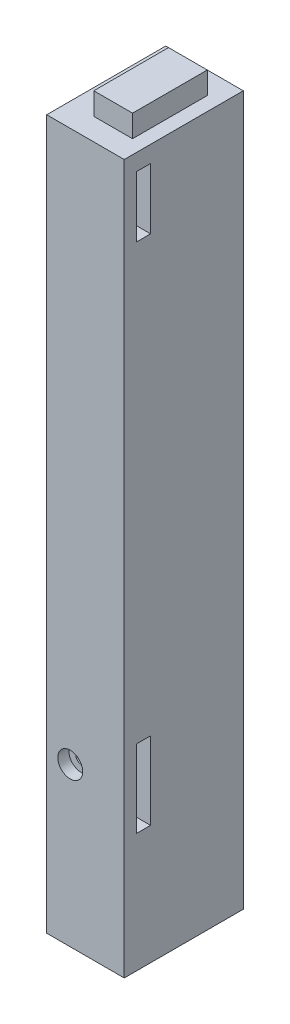
SolidWorks part; units mm, degrees
ref_plane "Front Plane" through (0, 0, 0) normal (0, 0, 1) x (1, 0, 0)
ref_plane "Top Plane" through (0, 0, 0) normal (0, 1, 0) x (1, 0, 0)
ref_plane "Right Plane" through (0, 0, 0) normal (1, 0, 0) x (0, 0, -1)
sketch "Sketch1" plane through (0, 0, 0) normal (0, 0, 1) x (1, 0, 0)
  line L1 (44.45, 406.4) -> (-44.45, 406.4)
  line L2 (44.45, 406.4) -> (44.45, -406.4)
  line L3 (44.45, -406.4) -> (-44.45, -406.4)
  line L4 (-44.45, 406.4) -> (-44.45, -406.4)
  line L5 (44.45, 406.4) -> (-44.45, -406.4) construction
  line L6 (44.45, -406.4) -> (-44.45, 406.4) construction
  point P0 (0, 0)
  dimension "D1" = 812.8
  dimension "D2" = 88.9
extrude "Boss-Extrude1" add sketch "Sketch1" along normal blind 136.525
sketch "Sketch2" plane through (0, 406.4, 0) normal (0, 1, 0) x (1, 0, 0)
  line L0 (-44.45, -136.525) -> (-44.45, 0) construction
  line L1 (-15.875, -25.4) -> (28.575, -25.4)
  line L2 (-15.875, -25.4) -> (-15.875, -111.125)
  line L3 (-15.875, -111.125) -> (28.575, -111.125)
  line L4 (28.575, -25.4) -> (28.575, -111.125)
  line L5 (-15.875, -25.4) -> (28.575, -111.125) construction
  line L6 (-15.875, -111.125) -> (28.575, -25.4) construction
  line L7 (44.45, 0) -> (-44.45, 0) construction
  point P0 (6.35, -68.2625)
  dimension "D1" = 85.725
  dimension "D2" = 28.575
  dimension "D3" = 44.45
  dimension "D4" = 25.4
extrude "Boss-Extrude2" add sketch "Sketch2" along normal blind 25.4 contours L2 L3 L4 L1
sketch "Sketch4" plane through (44.45, 0, 0) normal (1, 0, 0) x (0, 0, -1)
  line L0 (-136.525, 406.4) -> (0, 406.4) construction
  line L1 (-122.2375, -180.975) -> (-106.3625, -180.975)
  line L2 (-122.2375, -180.975) -> (-122.2375, -269.875)
  line L3 (-122.2375, -269.875) -> (-106.3625, -269.875)
  line L4 (-106.3625, -180.975) -> (-106.3625, -269.875)
  line L5 (-122.2375, -180.975) -> (-106.3625, -269.875) construction
  line L6 (-122.2375, -269.875) -> (-106.3625, -180.975) construction
  line L7 (-122.2375, 387.35) -> (-106.3625, 387.35)
  line L8 (-122.2375, 387.35) -> (-122.2375, 317.5)
  line L9 (-122.2375, 317.5) -> (-106.3625, 317.5)
  line L10 (-106.3625, 387.35) -> (-106.3625, 317.5)
  line L11 (-122.2375, 387.35) -> (-106.3625, 317.5) construction
  line L12 (-122.2375, 317.5) -> (-106.3625, 387.35) construction
  line L14 (-136.525, -406.4) -> (-136.525, 406.4) construction
  line L15 (-136.525, -406.4) -> (0, -406.4) construction
  point P0 (-114.3, -225.425)
  point P5 (-114.3, 352.425)
  point P12 (-102.9221, 352.425)
  point P17 (-68.2625, -406.4)
  dimension "D1" = 69.85
  dimension "D2" = 19.05
  dimension "D3" = 15.875
  dimension "D4" = 14.2875
  dimension "D5" = 88.9
  dimension "D6" = 136.525
  dimension "D7" = 15.875
extrude "Cut-Extrude1" cut sketch "Sketch4" against normal blind 50.8
sketch "Sketch5" plane through (0, 0, 0) normal (0, 0, -1) x (-1, 0, 0)
  line L0 (44.45, -406.4) -> (-44.45, -406.4) construction
  line L1 (30.1625, -184.15) -> (4.7625, -184.15)
  line L2 (30.1625, -184.15) -> (30.1625, -266.7)
  line L3 (30.1625, -266.7) -> (4.7625, -266.7)
  line L4 (4.7625, -184.15) -> (4.7625, -266.7)
  line L5 (30.1625, -184.15) -> (4.7625, -266.7) construction
  line L6 (30.1625, -266.7) -> (4.7625, -184.15) construction
  line L7 (44.45, 406.4) -> (44.45, -406.4) construction
  point P0 (17.4625, -225.425)
  dimension "D1" = 25.4
  dimension "D2" = 82.55
  dimension "D3" = 139.7
  dimension "D4" = 14.2875
extrude "Cut-Extrude2" cut sketch "Sketch5" against normal blind 50.8
sketch "Sketch6" plane through (0, 0, 136.525) normal (0, 0, 1) x (1, 0, 0)
  line L0 (-4.7625, -184.15) -> (-4.7625, -266.7) construction
  line L1 (-4.7625, -266.7) -> (-30.1625, -266.7) construction
  line L2 (-30.1625, -266.7) -> (-30.1625, -184.15) construction
  line L3 (-30.1625, -184.15) -> (-4.7625, -184.15) construction
  line L4 (44.45, -180.975) -> (44.45, -269.875) construction
  line L5 (44.45, -269.875) -> (-6.35, -269.875) construction
  line L6 (-6.35, -269.875) -> (-6.35, -180.975) construction
  line L7 (-6.35, -180.975) -> (44.45, -180.975) construction
  line L8 (44.45, 387.35) -> (44.45, 317.5) construction
  line L9 (44.45, 317.5) -> (-6.35, 317.5) construction
  line L10 (-6.35, 317.5) -> (-6.35, 387.35) construction
  line L11 (-6.35, 387.35) -> (44.45, 387.35) construction
  line L12 (-4.7625, -184.15) -> (-4.7625, -266.7)
  line L13 (-4.7625, -266.7) -> (-30.1625, -266.7)
  line L14 (-30.1625, -266.7) -> (-30.1625, -184.15)
  line L15 (-30.1625, -184.15) -> (-4.7625, -184.15)
  line L16 (44.45, -180.975) -> (44.45, -269.875)
  line L17 (44.45, -269.875) -> (-6.35, -269.875)
  line L18 (-6.35, -269.875) -> (-6.35, -180.975)
  line L19 (-6.35, -180.975) -> (44.45, -180.975)
  line L20 (44.45, 387.35) -> (44.45, 317.5)
  line L21 (44.45, 317.5) -> (-6.35, 317.5)
  line L22 (-6.35, 317.5) -> (-6.35, 387.35)
  line L23 (-6.35, 387.35) -> (44.45, 387.35)
  line L24 (-30.1625, -184.15) -> (-4.7625, -266.7) construction
  circle A0 centre (-17.4625, -225.425) radius 6.35
  circle A1 centre (-17.4625, -225.425) radius 14.2875
  dimension "D1" = 12.7
  dimension "D2" = 28.575
extrude "Cut-Extrude3" cut sketch "Sketch6" against normal blind 12.7 contours A1
sketch "Sketch7" plane through (0, 0, 123.825) normal (0, 0, 1) x (1, 0, 0)
  circle A0 centre (-17.4625, -225.425) radius 6.35
  dimension "D1" = 12.7
extrude "Cut-Extrude4" cut sketch "Sketch7" against normal through all
